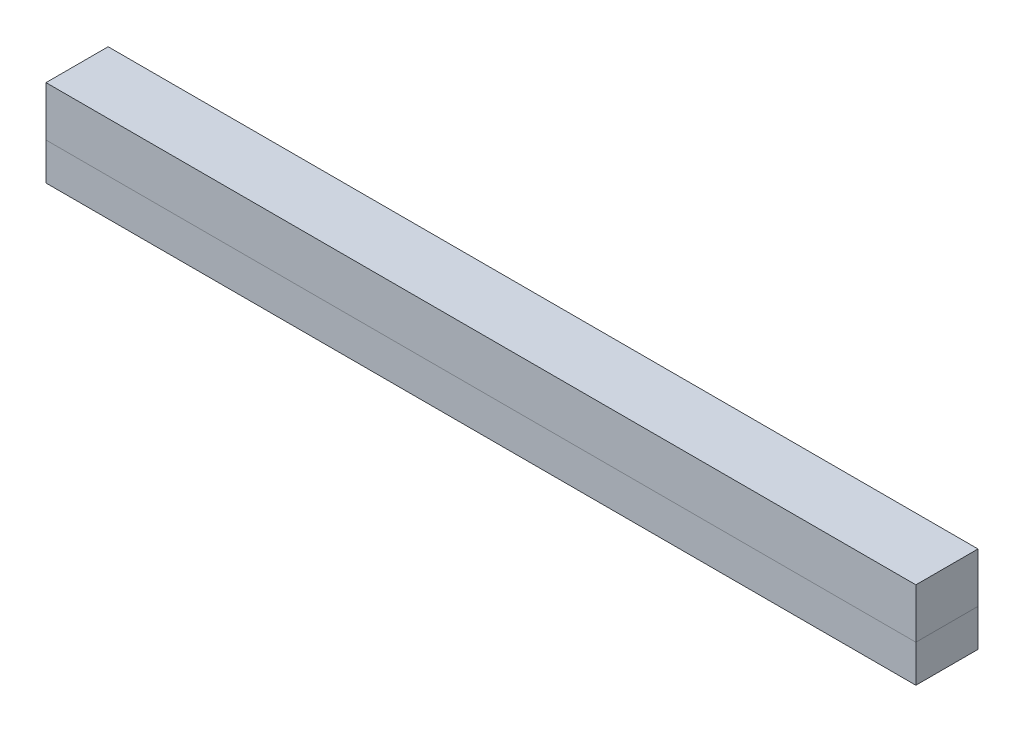
SolidWorks part; units mm, degrees
ref_plane "Front Plane" through (0, 0, 0) normal (0, 0, 1) x (1, 0, 0)
ref_plane "Top Plane" through (0, 0, 0) normal (0, 1, 0) x (1, 0, 0)
ref_plane "Right Plane" through (0, 0, 0) normal (1, 0, 0) x (0, 0, -1)
other "Configuration Table"
sketch "Sketch1" plane through (0, 0, 0) normal (0, 1, 0) x (1, 0, 0)
  line L1 (-7000, -500) -> (7000, -500)
  line L2 (-7000, -500) -> (-7000, 500)
  line L3 (-7000, 500) -> (7000, 500)
  line L4 (7000, -500) -> (7000, 500)
extrude "Boss-Extrude1" add sketch "Sketch1" along normal blind 800 separate body
sketch "Sketch2" plane through (0, 0, 0) normal (0, 1, 0) x (1, 0, 0)
  line L1 (-7000, -500) -> (7000, -500)
  line L2 (-7000, -500) -> (-7000, 500)
  line L3 (-7000, 500) -> (7000, 500)
  line L4 (7000, -500) -> (7000, 500)
extrude "Boss-Extrude2" add sketch "Sketch2" against normal blind 600 flip side to cut separate body
